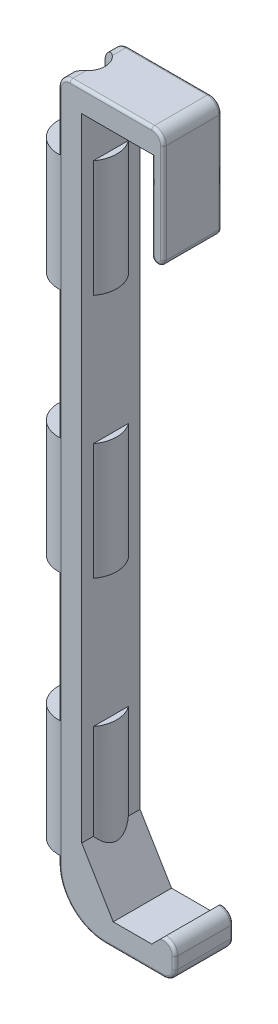
SolidWorks part; units mm, degrees
ref_plane "Front Plane" through (0, 0, 0) normal (0, 0, 1) x (1, 0, 0)
ref_plane "Top Plane" through (0, 0, 0) normal (0, 1, 0) x (1, 0, 0)
ref_plane "Right Plane" through (0, 0, 0) normal (1, 0, 0) x (0, 0, -1)
sketch "Sketch1" plane through (0, 0, 0) normal (0, 0, 1) x (1, 0, 0)
  line L0 (0, 0) -> (0, 62.65)
  line L1 (0, 62.65) -> (9, 62.65)
  line L2 (9, 62.65) -> (9, 52.65)
  line L3 (9, 52.65) -> (8, 52.65)
  line L4 (8, 52.65) -> (8, 60.65)
  line L5 (8, 60.65) -> (2, 60.65)
  line L6 (2, 60.65) -> (2, 6.5)
  line L7 (2, 0) -> (0, 0)
  line L8 (2, 0) -> (10, 0)
  line L9 (10, 0) -> (10, 3)
  line L10 (10, 3) -> (9, 3)
  line L11 (9, 3) -> (8, 2)
  line L12 (8, 2) -> (4.7, 2)
  line L13 (4.7, 2) -> (2, 6.5)
  dimension "D1" = 1
  dimension "D2" = 10
  dimension "D3" = 2
  dimension "D4" = 62.65
  dimension "D5" = 2
  dimension "D6" = 6
  dimension "D7" = 54.15
  dimension "D8" = 4.5
  dimension "D9" = 2.7
  dimension "D10" = 3.3
  dimension "D11" = 3
  dimension "D12" = 1
  dimension "D14" = 58.65
extrude "Boss-Extrude1" add sketch "Sketch1" along normal blind 5
fillet "Fillet1" radius 0.5 2 edges at (8, 52.65, 2.5) (9, 52.65, 2.5)
fillet "Fillet2" radius 1 4 edges at (9, 62.65, 2.5) (10, 3, 2.5) (10, 0, 2.5) (0, 62.65, 2.5)
fillet "Fillet3" radius 4 1 edges at (0, 0, 2.5)
fillet "Fillet4" radius 0.25 26 edges at (8, 56.9, 5) (8.1464, 52.7964, 5) (8.8536, 52.7964, 5) (9, 57.4, 5) (8.7071, 62.3571, 5) (4.5, 62.65, 5) (0.2929, 62.3571, 5) (0, 32.825, 5) (9.7071, 2.7071, 5) (10, 1.5, 5) (9.7071, 0.2929, 5) (6.5, 0, 5) (8, 56.9, 0) (8.1464, 52.7964, 0) (8.8536, 52.7964, 0) (9, 57.4, 0) (8.7071, 62.3571, 0) (4.5, 62.65, 0) (0.2929, 62.3571, 0) (9.7071, 2.7071, 0) (10, 1.5, 0) (9.7071, 0.2929, 0) (1.1716, 1.1716, 5) (6.5, 0, 0) (1.1716, 1.1716, 0) (0, 32.825, 0)
sketch "Sketch2" plane through (0, 62.65, 0) normal (0, 1, 0) x (1, 0, 0)
  line L0 (8, -0.25) -> (1, -0.25) construction
  line L1 (1, -4.75) -> (8, -4.75) construction
  line L2 (0, -4.75) -> (0, -0.25) construction
  circle A0 centre (0, -2.5) radius 1.5
  dimension "D1" = 3
  dimension "D4" = 0
  dimension "D2" = 2.25
  dimension "D3" = 2.25
extrude "Cut-Extrude2" cut sketch "Sketch2" against normal through all
sketch "Sketch5" plane through (0, 62.65, 0) normal (0, 1, 0) x (1, 0, 0)
  circle A0 centre (0, -2.5) radius 1.5
  circle A1 centre (0, -2.5) radius 2.5
  dimension "D1" = 3
  dimension "D2" = 5
extrude "Boss-Extrude4" add sketch "Sketch5" along normal blind 10 from offset 16 offset against normal yes
pattern_linear "LPattern2" count 3 spacing 21 along (0, -1, 0) of "Boss-Extrude4", "Cut-Extrude2"
